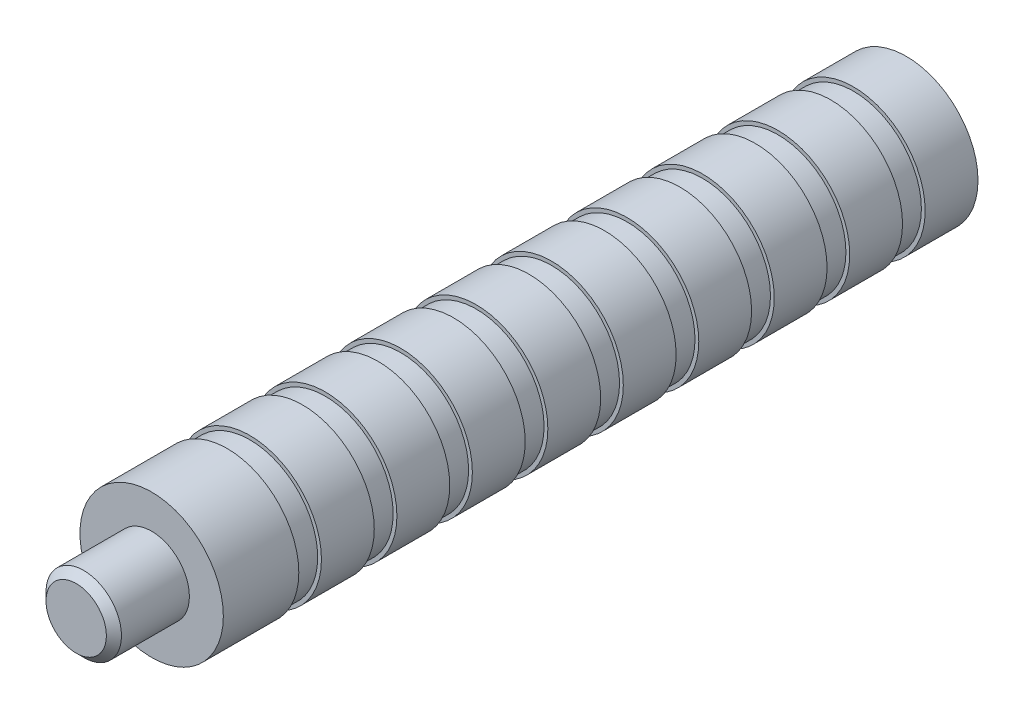
SolidWorks part; units mm, degrees
ref_plane "Front Plane" through (0, 0, 0) normal (0, 0, 1) x (1, 0, 0)
ref_plane "Top Plane" through (0, 0, 0) normal (0, 1, 0) x (1, 0, 0)
ref_plane "Right Plane" through (0, 0, 0) normal (1, 0, 0) x (0, 0, -1)
sketch "Sketch2" plane through (0, 0, 0) normal (1, 0, 0) x (0, 0, -1)
  line L0 (-25, 0) -> (25, 0)
  line L1 (-25, 0) -> (-25, 4.75)
  line L2 (-25, 4.75) -> (-20, 4.75)
  line L3 (25, 4.75) -> (25, 0)
  line L4 (-20, 4.75) -> (-20, 4.5)
  line L5 (-20, 4.5) -> (-18.5, 4.5)
  line L6 (-18.5, 4.5) -> (-18.5, 4.75)
  line L7 (-15, 4.75) -> (-15, 4.5)
  line L8 (-15, 4.5) -> (-13.5, 4.5)
  line L9 (-13.5, 4.5) -> (-13.5, 4.75)
  line L10 (-10, 4.75) -> (-10, 4.5)
  line L11 (-10, 4.5) -> (-8.5, 4.5)
  line L12 (-8.5, 4.5) -> (-8.5, 4.75)
  line L13 (-5, 4.75) -> (-5, 4.5)
  line L14 (-5, 4.5) -> (-3.5, 4.5)
  line L15 (-3.5, 4.5) -> (-3.5, 4.75)
  line L16 (0, 4.75) -> (0, 4.5)
  line L17 (0, 4.5) -> (1.5, 4.5)
  line L18 (1.5, 4.5) -> (1.5, 4.75)
  line L19 (5, 4.75) -> (5, 4.5)
  line L20 (5, 4.5) -> (6.5, 4.5)
  line L21 (6.5, 4.5) -> (6.5, 4.75)
  line L22 (10, 4.75) -> (10, 4.5)
  line L23 (10, 4.5) -> (11.5, 4.5)
  line L24 (11.5, 4.5) -> (11.5, 4.75)
  line L25 (15, 4.75) -> (15, 4.5)
  line L26 (15, 4.5) -> (16.5, 4.5)
  line L27 (16.5, 4.5) -> (16.5, 4.75)
  line L28 (20, 4.75) -> (20, 4.5)
  line L29 (20, 4.5) -> (21.5, 4.5)
  line L30 (21.5, 4.5) -> (21.5, 4.75)
  line L31 (-18.5, 4.75) -> (-15, 4.75)
  line L32 (-13.5, 4.75) -> (-10, 4.75)
  line L33 (-8.5, 4.75) -> (-5, 4.75)
  line L34 (-3.5, 4.75) -> (0, 4.75)
  line L35 (1.5, 4.75) -> (5, 4.75)
  line L36 (6.5, 4.75) -> (10, 4.75)
  line L37 (11.5, 4.75) -> (15, 4.75)
  line L38 (25, 0) -> (30.5762, 0) construction
  line L39 (16.5, 4.75) -> (20, 4.75)
  line L40 (21.5, 4.75) -> (25, 4.75)
  point P4 (0, 0)
  point P9 (-20, 4.625)
  dimension "D1" = 50
  dimension "D2" = 4.75
  dimension "D3" = 1.5
  dimension "D4" = 0.25
  dimension "D5" = 5
  dimension "D6" = 9
revolve "Revolve2" add sketch "Sketch2" angle 360 about L38
sketch "Sketch3" plane through (0, 0, -25) normal (0, 0, -1) x (-1, 0, 0)
  line L1 (1.75, 0.9682) -> (1.75, -0.9682)
  arc A0 (1.75, 0.9682) -> (1.75, -0.9682) centre (0, 0) ccw
  dimension "D1" = 4
  dimension "D2" = 1.75
extrude "Cut-Extrude1" cut sketch "Sketch3" against normal blind 14
sketch "Sketch4" plane through (0, 0, 25) normal (0, 0, 1) x (1, 0, 0)
  circle A0 centre (0, 0) radius 2.5
  dimension "D1" = 5
extrude "Boss-Extrude2" add sketch "Sketch4" along normal blind 5
fillet "Chamfer1" radius 0.5 1 edges at (2.5, 0, 30) type face fillet profile chamfer first side face at (2.5, 0, 30) second side face at (2.5, 0, 30)
